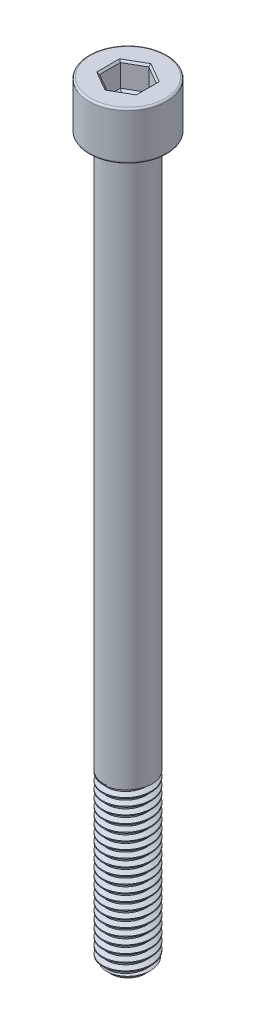
SolidWorks part; units mm, degrees
material "AISI Type A2 Tool Steel"
ref_plane "Front Plane" through (0, 0, 0) normal (0, 0, 1) x (1, 0, 0)
ref_plane "Top Plane" through (0, 0, 0) normal (0, 1, 0) x (1, 0, 0)
ref_plane "Right Plane" through (0, 0, 0) normal (1, 0, 0) x (0, 0, -1)
sketch "Sketch1" plane through (0, 0, 0) normal (0, 1, 0) x (1, 0, 0)
  circle A0 centre (0, 0) radius 4
  dimension "D1" = 8
extrude "Boss-Extrude1" add sketch "Sketch1" along normal blind 28
thread "Thread1" pitch 1.25 method cut profile "Thread Profile1" start angle 0, offset 2, length 0, pitch 1.25, diameter 8
ref_plane "Plane1" through (-4, 30, 0) normal (0, 0, 1) x (-1, 0, 0)
sketch "Thread Profile1" plane through (-4, 30, 0) normal (0, 0, 1) x (-1, 0, 0)
  line L0 (0, 0) -> (0, 1.25) construction
  line L11 (0, 0) -> (0, 1.0937)
  line L12 (0, 1.0937) -> (-0.6766, 0.7031)
  line L13 (-0.6766, 0.7031) -> (-0.6766, 0.3906)
  line L15 (-0.6766, 0.3906) -> (0, 0)
  line L17 (-0.6766, 0.5469) -> (0, 0.5469) construction
  point P2 (0, 0)
  dimension "Pitch" = 1.25
  dimension "Profile_Angle" = 60
  dimension "Profile_Land" = 0.3125
  dimension "Profile_Height" = 0.6766
sketch "Sketch2" plane through (0, 28, 0) normal (0, 1, 0) x (1, 0, 0)
  circle A0 centre (0, 0) radius 4
  dimension "D1" = 8
extrude "Boss-Extrude2" add sketch "Sketch2" along normal blind 92
sketch "Sketch5" plane through (0, 120, 0) normal (0, 1, 0) x (1, 0, 0)
  circle A0 centre (0, 0) radius 6.5
  dimension "D1" = 13
extrude "Boss-Extrude3" add sketch "Sketch5" along normal blind 8
sketch "Sketch6" plane through (0, 0, 0) normal (0, 0, 1) x (1, 0, 0)
  line L0 (0, 0) -> (0, 0.7245) construction
  line L1 (0, 0) -> (4.01, 0) construction
  line L2 (4.01, 0) -> (4.01, 1.2)
  line L3 (4.01, 1.2) -> (2.81, 0)
  line L4 (2.81, 0) -> (4.01, 0)
  dimension "D1" = 1.2
  dimension "D2" = 45
  dimension "D3" = 4.01
revolve "Cut-Revolve1" cut sketch "Sketch6" angle 360 about L0
fillet "Fillet1" radius 0.3 2 edges at (0, 120, 6.5) (0, 128, 6.5)
sketch "Sketch7" plane through (0, 128, 0) normal (0, 1, 0) x (1, 0, 0)
  line L1 (0, 3.4641) -> (-3, 1.7321)
  line L2 (-3, 1.7321) -> (-3, -1.7321)
  line L3 (-3, -1.7321) -> (0, -3.4641)
  line L4 (0, -3.4641) -> (3, -1.7321)
  line L5 (3, -1.7321) -> (3, 1.7321)
  line L6 (3, 1.7321) -> (0, 3.4641)
  circle A0 centre (0, 0) radius 3 construction
  dimension "D1" = 6
extrude "Cut-Extrude1" cut sketch "Sketch7" against normal blind 4
chamfer "Chamfer1" distance 0.3 angle 45 6 edges at (-3, 128, 0) (-1.5, 128, 2.5981) (1.5, 128, 2.5981) (3, 128, 0) (1.5, 128, -2.5981) (-1.5, 128, -2.5981)
sketch "Sketch8" plane through (0, 124, 0) normal (0, 1, 0) x (1, 0, 0)
  line L1 (0, 3.4641) -> (-3, 1.7321)
  line L2 (-3, 1.7321) -> (-3, -1.7321)
  line L3 (-3, -1.7321) -> (0, -3.4641)
  line L4 (0, -3.4641) -> (3, -1.7321)
  line L5 (3, -1.7321) -> (3, 1.7321)
  line L6 (3, 1.7321) -> (0, 3.4641)
  circle A0 centre (0, 0) radius 3 construction
extrude "Cut-Extrude2" cut sketch "Sketch8" against normal blind 0.4 draft 60
